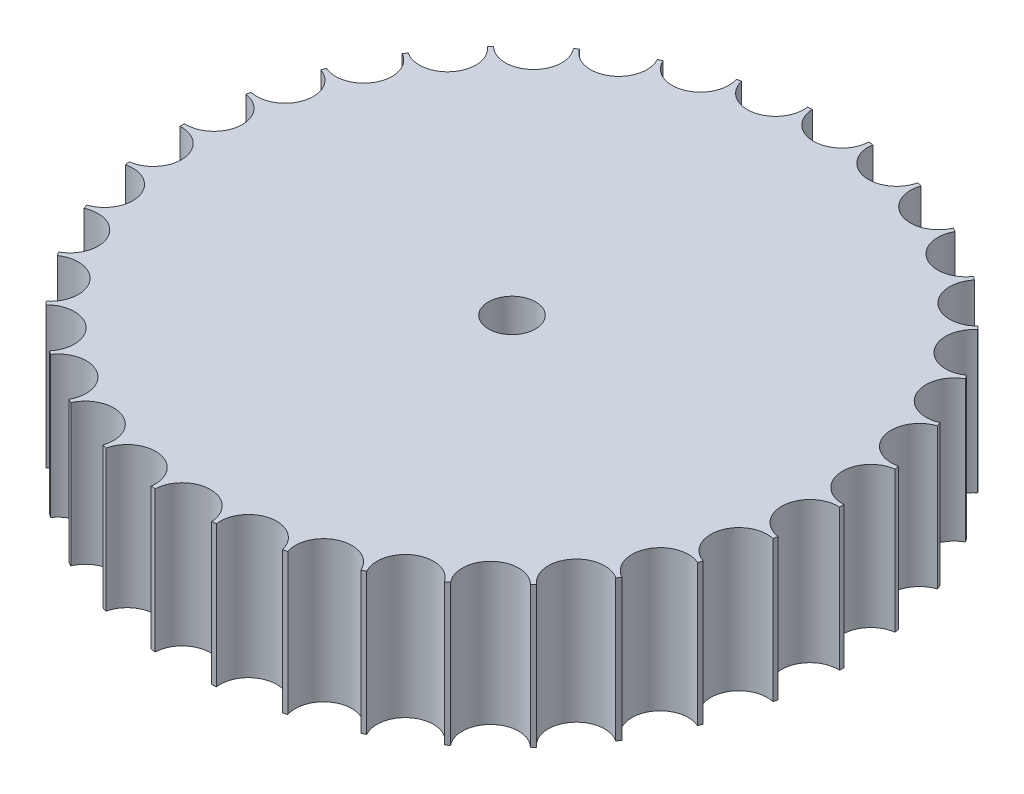
SolidWorks part; units mm, degrees
ref_plane "Front Plane" through (0, 0, 0) normal (0, 0, 1) x (1, 0, 0)
ref_plane "Top Plane" through (0, 0, 0) normal (0, 1, 0) x (1, 0, 0)
ref_plane "Right Plane" through (0, 0, 0) normal (1, 0, 0) x (0, 0, -1)
sketch "Sketch1" plane through (0, 0, 0) normal (0, 1, 0) x (1, 0, 0)
  arc A0 (-2.9972, 34.8714) -> (2.9972, 34.8714) centre (0, 35) ccw
  circle A1 centre (0, 0) radius 35
  arc A2 (3.4614, 34.8284) -> (9.3538, 33.7269) centre (6.4312, 34.4041) ccw
  arc A3 (9.8022, 33.5994) -> (15.3919, 31.4339) centre (12.6435, 32.6365) ccw
  arc A4 (15.8091, 31.2261) -> (20.9057, 28.0704) centre (18.4251, 29.7576) ccw
  arc A5 (21.2777, 27.7895) -> (25.7077, 23.7511) centre (23.5793, 25.8653) ccw
  arc A6 (26.0218, 23.4066) -> (29.6342, 18.6229) centre (27.9306, 21.0922) ccw
  arc A7 (29.8796, 18.2266) -> (32.5516, 12.8605) centre (31.3307, 15.6008) ccw
  arc A8 (32.72, 12.4258) -> (34.3605, 6.6602) centre (33.6639, 9.5782) ccw
  arc A9 (34.4461, 6.202) -> (34.9992, 0.2331) centre (34.8507, 3.2294) ccw
  arc A10 (34.9992, -0.2331) -> (34.4461, -6.202) centre (34.8507, -3.2294) ccw
  arc A11 (34.3605, -6.6602) -> (32.72, -12.4258) centre (33.6639, -9.5782) ccw
  arc A12 (32.5516, -12.8605) -> (29.8796, -18.2266) centre (31.3307, -15.6008) ccw
  arc A13 (29.6342, -18.6229) -> (26.0218, -23.4066) centre (27.9306, -21.0922) ccw
  arc A14 (25.7077, -23.7511) -> (21.2777, -27.7895) centre (23.5793, -25.8653) ccw
  arc A15 (20.9057, -28.0704) -> (15.8091, -31.2261) centre (18.4251, -29.7576) ccw
  arc A16 (15.3919, -31.4339) -> (9.8022, -33.5994) centre (12.6435, -32.6365) ccw
  arc A17 (9.3538, -33.7269) -> (3.4614, -34.8284) centre (6.4312, -34.4041) ccw
  arc A18 (2.9972, -34.8714) -> (-2.9972, -34.8714) centre (0, -35) ccw
  arc A19 (-3.4614, -34.8284) -> (-9.3538, -33.7269) centre (-6.4312, -34.4041) ccw
  arc A20 (-9.8022, -33.5994) -> (-15.3919, -31.4339) centre (-12.6435, -32.6365) ccw
  arc A21 (-15.8091, -31.2261) -> (-20.9057, -28.0704) centre (-18.4251, -29.7576) ccw
  arc A22 (-21.2777, -27.7895) -> (-25.7077, -23.7511) centre (-23.5793, -25.8653) ccw
  arc A23 (-26.0218, -23.4066) -> (-29.6342, -18.6229) centre (-27.9306, -21.0922) ccw
  arc A24 (-29.8796, -18.2266) -> (-32.5516, -12.8605) centre (-31.3307, -15.6008) ccw
  arc A25 (-32.72, -12.4258) -> (-34.3605, -6.6602) centre (-33.6639, -9.5782) ccw
  arc A26 (-34.4461, -6.202) -> (-34.9992, -0.2331) centre (-34.8507, -3.2294) ccw
  arc A27 (-34.9992, 0.2331) -> (-34.4461, 6.202) centre (-34.8507, 3.2294) ccw
  arc A28 (-34.3605, 6.6602) -> (-32.72, 12.4258) centre (-33.6639, 9.5782) ccw
  circle A29 centre (0, 0) radius 2.5
  arc A30 (-32.5516, 12.8605) -> (-29.8796, 18.2266) centre (-31.3307, 15.6008) ccw
  arc A31 (-29.6342, 18.6229) -> (-26.0218, 23.4066) centre (-27.9306, 21.0922) ccw
  arc A32 (-25.7077, 23.7511) -> (-21.2777, 27.7895) centre (-23.5793, 25.8653) ccw
  arc A33 (-20.9057, 28.0704) -> (-15.8091, 31.2261) centre (-18.4251, 29.7576) ccw
  arc A34 (-15.3919, 31.4339) -> (-9.8022, 33.5994) centre (-12.6435, 32.6365) ccw
  arc A35 (-9.3538, 33.7269) -> (-3.4614, 34.8284) centre (-6.4312, 34.4041) ccw
  point P8 (0, 32)
  point P90 (0, 0)
  dimension "D2" = 70
  dimension "D4" = 5
  dimension "D1" = 3
  dimension "D3" = 34
extrude "Boss-Extrude1" add sketch "Sketch1" along normal blind 15 contours A1 A26 A25 A24 A23 A22 A21 A20 A19 A18 A17 A16 A15 A14 A13 A12 A11 A10 A9 A8 A7 A6 A5 A4 A3 region at (0, 0, -31.0119)
